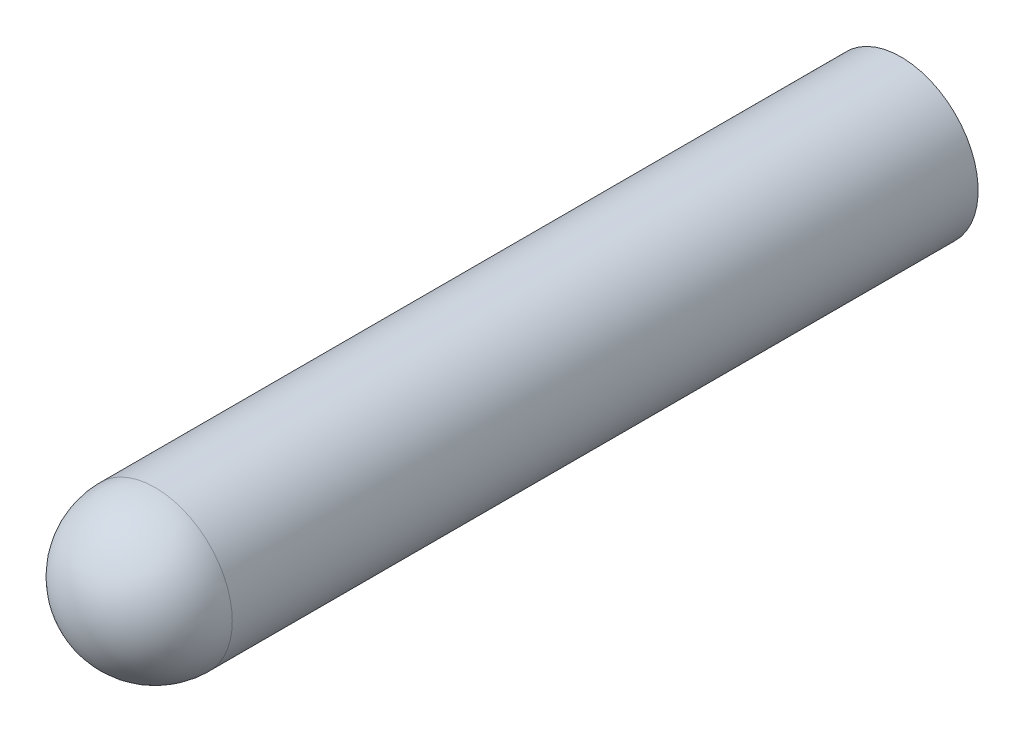
SolidWorks part; units mm, degrees
ref_plane "Płaszczyzna przednia" through (0, 0, 0) normal (0, 0, 1) x (1, 0, 0)
ref_plane "Płaszczyzna górna" through (0, 0, 0) normal (0, 1, 0) x (1, 0, 0)
ref_plane "Płaszczyzna prawa" through (0, 0, 0) normal (1, 0, 0) x (0, 0, -1)
sketch "Sketch1" plane through (0, 0, 0) normal (0, 0, 1) x (1, 0, 0)
  circle A0 centre (0, 0) radius 1.5
  dimension "D1" = 3
extrude "Boss-Extrude1" add sketch "Sketch1" along normal blind 14.5
dome "Dome1" faces to dome 1 distance 1.5 reverse direction no elliptical dome no face at (1.5, 0, 14.5) parameters "D1"=1.5
